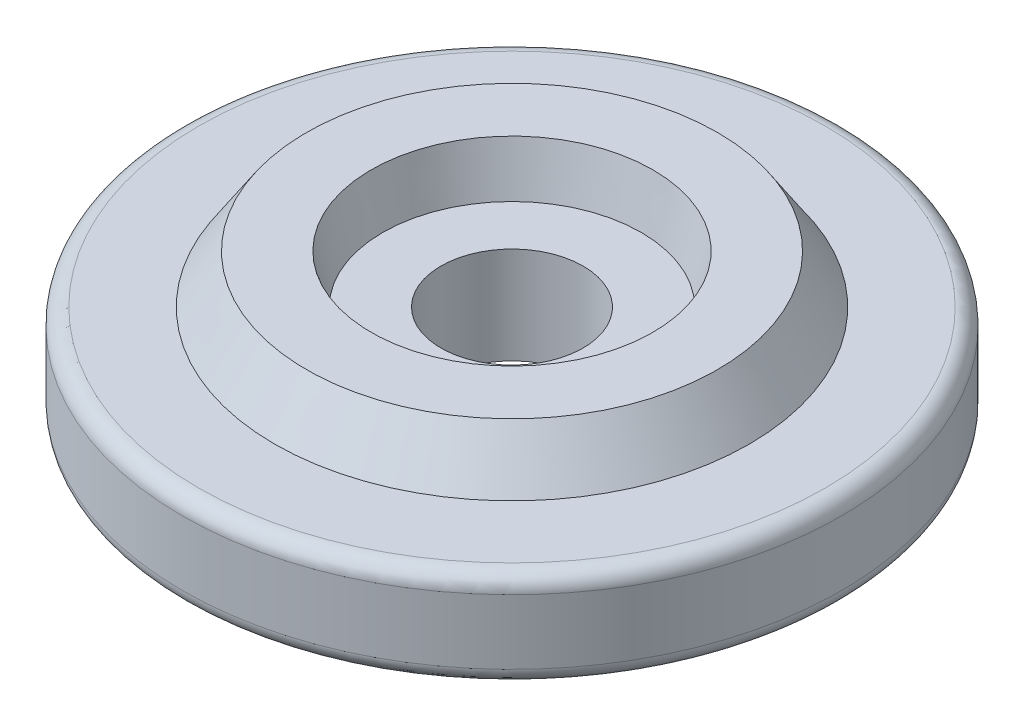
SolidWorks part; units mm, degrees
ref_plane "Front Plane" through (0, 0, 0) normal (0, 0, 1) x (1, 0, 0)
ref_plane "Top Plane" through (0, 0, 0) normal (0, 1, 0) x (1, 0, 0)
ref_plane "Right Plane" through (0, 0, 0) normal (1, 0, 0) x (0, 0, -1)
sketch "Sketch1" plane through (0, 0, 0) normal (0, 0, 1) x (1, 0, 0)
  line L0 (2.2, 0) -> (2.2, 3)
  line L1 (2.2, 3) -> (4, 3)
  line L2 (4, 3) -> (4.3594, 4.5)
  line L3 (4.3594, 4.5) -> (6.3594, 4.5)
  line L4 (6.3594, 4.5) -> (7.348, 3)
  line L5 (7.348, 3) -> (9.7, 3)
  line L6 (10.2, 2.5) -> (10.2, 0.5)
  line L7 (9.7, 0) -> (2.2, 0)
  line L8 (0, 0) -> (0, 4.2807) construction
  arc A0 (10.2, 0.5) -> (9.7, 0) centre (9.7, 0.5) cw
  arc A1 (9.7, 3) -> (10.2, 2.5) centre (9.7, 2.5) cw
  point P19 (10.2, 0)
  point P22 (10.2, 3)
  dimension "D7" = 0.5
  dimension "D1" = 10.2
  dimension "D2" = 2.2
  dimension "D3" = 4
  dimension "D4" = 3
  dimension "D5" = 4.5
  dimension "D6" = 2
revolve "Revolve1" add sketch "Sketch1" angle 360 about L8
